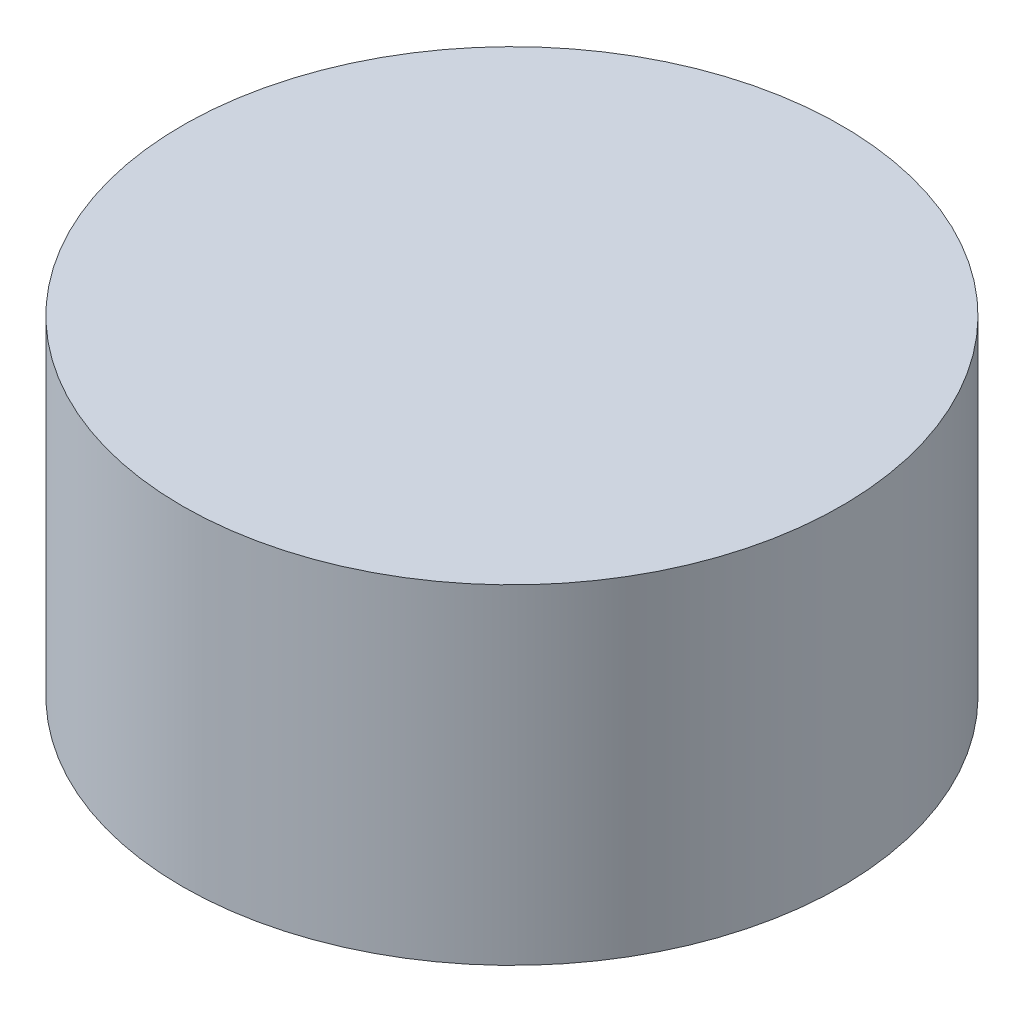
SolidWorks part; units mm, degrees
material "Zinc AC41A Alloy, As Cast"
ref_plane "Front Plane" through (0, 0, 0) normal (0, 0, 1) x (1, 0, 0)
ref_plane "Top Plane" through (0, 0, 0) normal (0, 1, 0) x (1, 0, 0)
ref_plane "Right Plane" through (0, 0, 0) normal (1, 0, 0) x (0, 0, -1)
sketch "Sketch1" plane through (0, 0, 0) normal (0, 1, 0) x (1, 0, 0)
  circle A0 centre (0, 0) radius 3.175
  dimension "D1" = 6.35
extrude "Boss-Extrude1" add sketch "Sketch1" along normal blind 3.175
ref_axis "Axis1" through (0, 3.175, 0) along (0, -1, 0)
